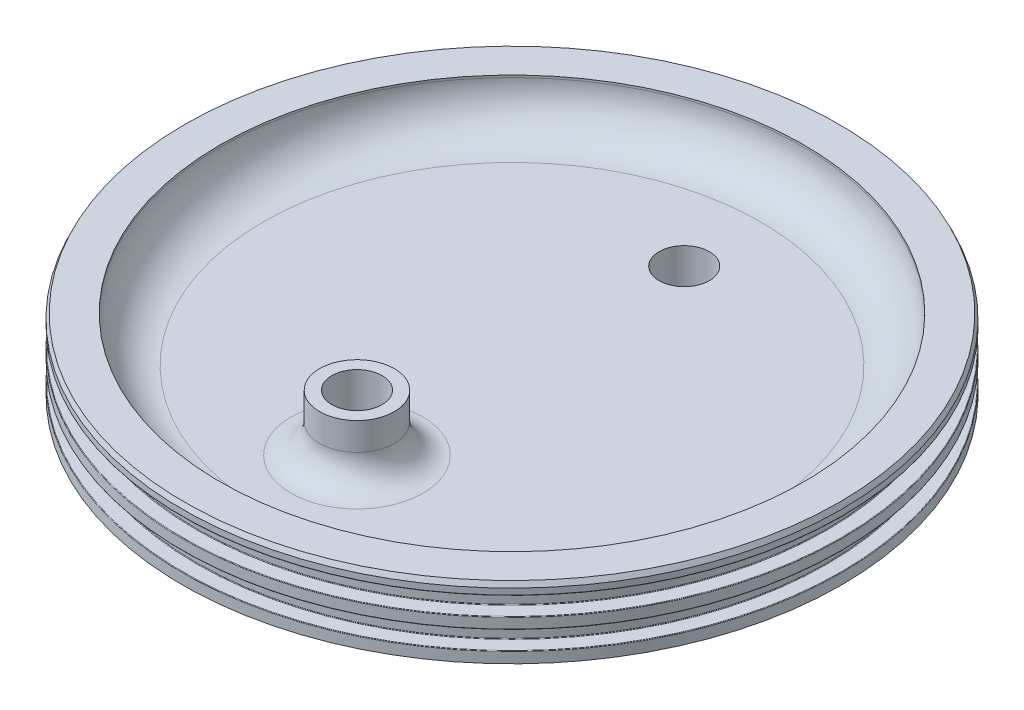
SolidWorks part; units mm, degrees
material "6061-T6 (SS)"
ref_plane "Front Plane" through (0, 0, 0) normal (0, 0, 1) x (1, 0, 0)
ref_plane "Top Plane" through (0, 0, 0) normal (0, 1, 0) x (1, 0, 0)
ref_plane "Right Plane" through (0, 0, 0) normal (1, 0, 0) x (0, 0, -1)
sketch "Sketch1" plane through (0, 0, 0) normal (0, 0, 1) x (1, 0, 0)
  line L0 (0, 48.1922) -> (0, -25.6743) construction
  line L1 (0, 0) -> (72.898, 0)
  line L2 (72.898, 0) -> (72.898, 2.4638)
  line L3 (72.898, 2.4638) -> (69.6468, 2.4638)
  line L4 (69.6468, 2.4638) -> (69.6468, 6.5278)
  line L5 (69.6468, 6.5278) -> (72.898, 6.5278)
  line L6 (72.898, 6.5278) -> (72.898, 8.9916)
  line L7 (72.898, 8.9916) -> (69.6468, 8.9916)
  line L8 (64.5668, 15.5956) -> (64.5668, 5.588)
  line L9 (64.5668, 5.588) -> (0, 5.588)
  line L10 (0, 5.588) -> (0, 0)
  line L11 (69.6468, 8.9916) -> (69.6468, 13.0556)
  line L12 (69.6468, 13.0556) -> (72.898, 13.0556)
  line L13 (72.898, 13.0556) -> (72.898, 15.5956)
  line L14 (72.898, 15.5956) -> (64.5668, 15.5956)
  dimension "D1" = 145.796
  dimension "D2" = 4.064
  dimension "D5" = 5.588
  dimension "D7" = 4.064
  dimension "D4" = 2.4638
  dimension "D8" = 2.54
  dimension "D3" = 69.6468
  dimension "D6" = 5.08
revolve "Revolve1" add sketch "Sketch1" angle 360 about L0
sketch "Sketch6" plane through (0, 0, 0) normal (0, -1, 0) x (1, 0, 0)
  circle A0 centre (0, 0) radius 66.04
  dimension "D1" = 132.08
extrude "Boss-Extrude1" add sketch "Sketch6" along normal blind 2.54
hole_wizard "Pipe Tap Drill for 1/4 Tap - GN2" positions "Sketch2" profile "Sketch3" hole size "1/4" standard "ANSI Inch" end condition through all
sketch "Sketch2" plane through (0, 5.588, 0) normal (0, 1, 0) x (1, 0, 0)
  point P4 (0, -34.29)
  dimension "D1" = 34.29
sketch "Sketch3" plane through (0, 5.588, 34.29) normal (1, 0, 0) x (0, 0, 1)
  line L0 (0, 0) -> (0, 8.128)
  line L1 (0, 8.128) -> (5.5626, 8.128)
  line L2 (5.5626, 8.128) -> (5.5626, 0)
  line L5 (5.5626, 0) -> (0, 0)
  line L11 (0, -6.35) -> (0, 107.95) construction
  dimension "Thru Hole Dia." = 11.1252
  dimension "Thru Hole Depth" = 8.128
fillet "CNC ID Fillet" radius 0.127 5 edges at (-69.6468, 6.5278, 0) (-69.6468, 2.4638, 0) (-69.6468, 13.0556, 0) (-69.6468, 8.9916, 0) (66.04, 0, 0)
fillet "CNC OD Fillet" radius 0.127 5 edges at (-72.898, 6.5278, 0) (-72.898, 2.4638, 0) (66.04, -2.54, 0) (-72.898, 13.0556, 0) (-72.898, 8.9916, 0)
chamfer "CNC Chamfers" distance 0.508 angle 65 1 edges at (-72.898, 15.5956, 0) first distance on face at (-64.5668, 15.5956, 0)
hole_wizard "Pipe Tap Drill for 1/4 Tap - Relief Valve" positions "Sketch13" profile "Sketch14" hole size "1/4" standard "ANSI Inch" end condition through all
sketch "Sketch13" plane through (0, -2.54, 0) normal (0, -1, 0) x (-1, 0, 0)
  point P4 (0, 38.1)
  dimension "D1" = 38.1
sketch "Sketch14" plane through (0, -2.54, -38.1) normal (1, 0, 0) x (0, 0, -1)
  line L0 (0, 0) -> (0, 18.1356)
  line L1 (0, 18.1356) -> (5.5626, 18.1356)
  line L2 (5.5626, 18.1356) -> (5.5626, 0)
  line L5 (5.5626, 0) -> (0, 0)
  line L11 (0, -6.35) -> (0, 107.95) construction
  dimension "Thru Hole Dia." = 11.1252
  dimension "Thru Hole Depth" = 18.1356
sketch "Sketch15" plane through (0, -2.54, 0) normal (0, -1, 0) x (1, 0, 0)
  circle A0 centre (0, 34.29) radius 8.255
  circle A1 centre (0, 34.29) radius 5.5626 construction
  circle A2 centre (0, 34.29) radius 5.5626
  dimension "D1" = 16.51
extrude "Boss-Extrude2" add sketch "Sketch15" against normal blind 12.446 from surface starting at face at (5.5626, 5.588, -38.1)
fillet "Fillet2" radius 6.35 1 edges at (8.255, 5.588, 34.29)
fillet "Fillet3" radius 9.525 1 edges at (-64.5668, 5.588, 0)
sketch "Sketch16" plane through (0, -2.54, 0) normal (0, -1, 0) x (1, 0, 0)
  line L0 (0, 34.29) -> (0, -38.1) construction
  line L1 (25.4, 26.67) -> (-25.4, 26.67) construction
  line L2 (-9.4223, -1.905) -> (9.4223, -1.905) construction
  line L3 (25.4, -30.48) -> (-25.4, -30.48) construction
  text T0 "GN2"
  text T1 "VENT\r\n"
  point P7 (0, 26.67)
  point P14 (0, -1.905)
  dimension "D1" = 50.8
  dimension "D2" = 7.62
equation "\"D3@Sketch1\"=5.484/2"
